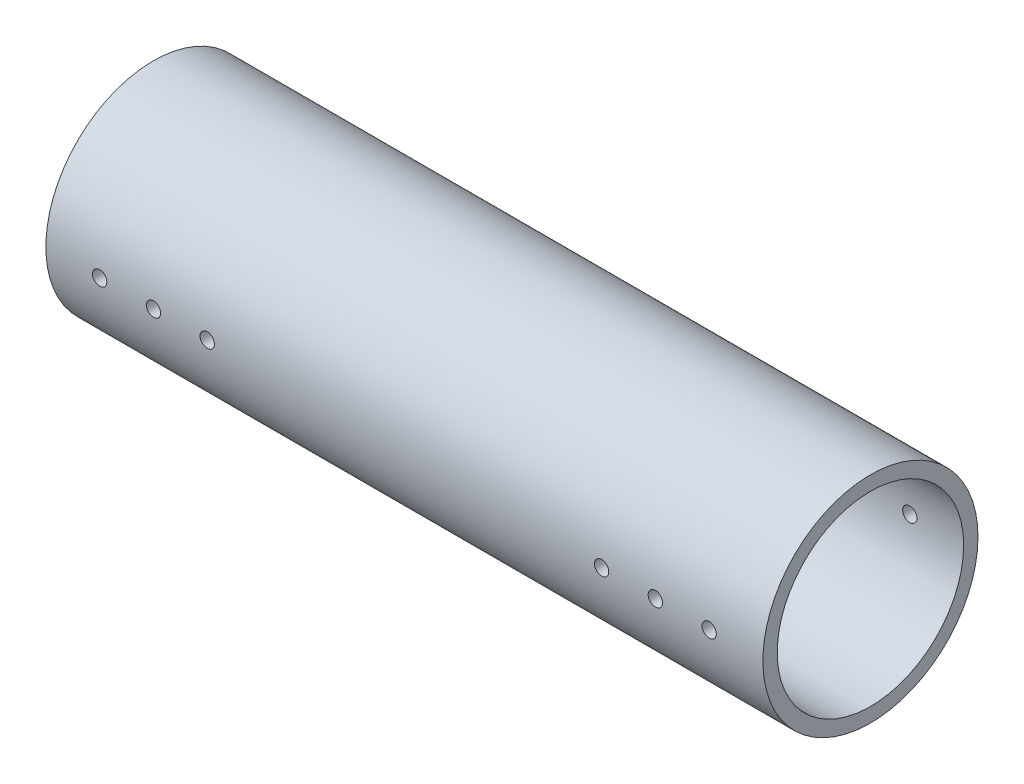
SolidWorks part; units mm, degrees
material "Zoltek Panex 33"
ref_plane "Спереди" through (0, 0, 0) normal (0, 0, 1) x (1, 0, 0)
ref_plane "Сверху" through (0, 0, 0) normal (0, 1, 0) x (1, 0, 0)
ref_plane "Справа" through (0, 0, 0) normal (1, 0, 0) x (0, 0, -1)
other "Configuration Table"
sketch "Эскиз2" plane through (0, 0, 0) normal (1, 0, 0) x (0, 0, -1)
  circle A0 centre (0, 0) radius 30
  circle A1 centre (0, 0) radius 26
  dimension "D1" = 60
  dimension "D2" = 52
extrude "Бобышка-Вытянуть2" add sketch "Эскиз2" along normal blind 200
ref_plane "Плоскость1" through (0, 0, 25) normal (0, 0, 1) x (1, 0, 0)
sketch "Эскиз4" plane through (0, 0, 25) normal (0, 0, 1) x (1, 0, 0)
  line L0 (0, -30) -> (200, -30) construction
  line L1 (200, -30) -> (200, 30) construction
  circle A0 centre (15, 0) radius 2
  circle A1 centre (185, 0) radius 2
  circle A2 centre (30, 0) radius 2
  circle A3 centre (45, 0) radius 2
  circle A4 centre (170, 0) radius 2
  circle A5 centre (155, 0) radius 2
  point P15 (0, 0)
  dimension "D1" = 4
  dimension "D4" = 4
  dimension "D6" = 4
  dimension "D8" = 4
  dimension "D10" = 4
  dimension "D11" = 4
  dimension "D2" = 15
  dimension "D3" = 30
  dimension "D5" = 15
  dimension "D7" = 15
  dimension "D9" = 15
  dimension "15" = 15
  dimension "D12" = 15
extrude "Вырез-Вытянуть2" cut sketch "Эскиз4" against normal through all and the other way blind 10 contours A0 | A1 | A2 | A3 | A5 | A4
equation "\"Diameter\"= 60мм"
equation "\"D1@Эскиз2\"= \"Diameter\""
equation "\"Length\"= 200мм"
equation "\"Thickness\"= 4мм"
equation "\"D1@Бобышка-Вытянуть2\"= \"Length\""
equation "\"D2@Эскиз2\" = \"Diameter\" - \"Thickness\" * 2"
equation "\"D4@Эскиз4\"=\"D1@Эскиз4\""
equation "\"D5@Эскиз4\"=\"D2@Эскиз4\""
equation "\"D3@Эскиз4\"=\"Diameter\"/2"
equation "\"D6@Эскиз4\"=\"D1@Эскиз4\""
equation "\"D8@Эскиз4\"=\"D6@Эскиз4\""
equation "\"D10@Эскиз4\"=\"D4@Эскиз4\""
equation "\"D11@Эскиз4\"=\"D4@Эскиз4\""
